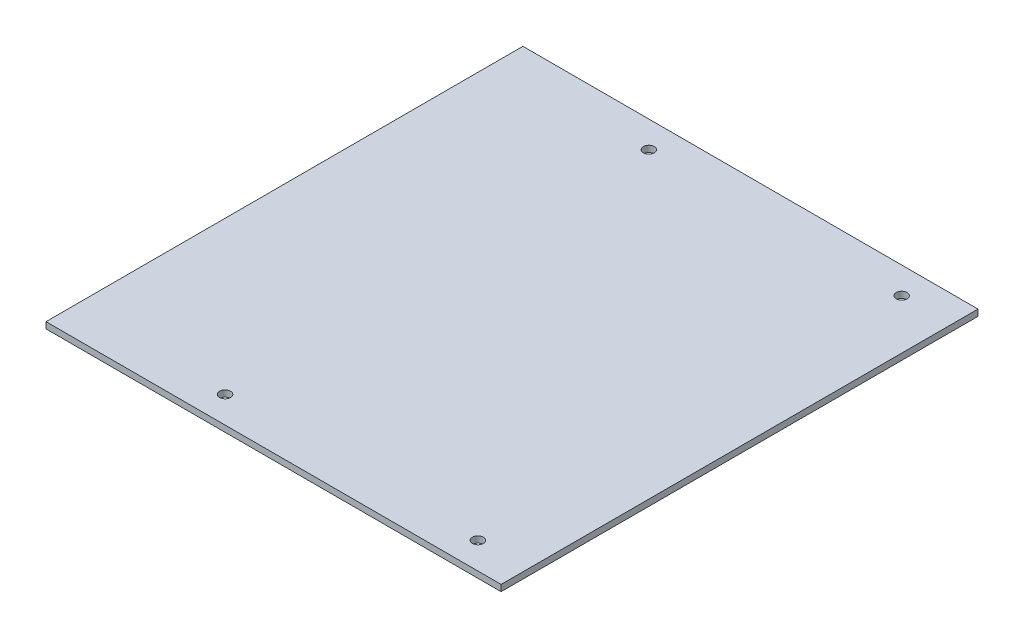
SolidWorks part; units mm, degrees
ref_plane "Front Plane" through (0, 0, 0) normal (0, 0, 1) x (1, 0, 0)
ref_plane "Top Plane" through (0, 0, 0) normal (0, 1, 0) x (1, 0, 0)
ref_plane "Right Plane" through (0, 0, 0) normal (1, 0, 0) x (0, 0, -1)
sketch "Sketch1" plane through (0, 0, 0) normal (0, 1, 0) x (1, 0, 0)
  line L1 (-140.35, -119.775) -> (-368.95, -119.775)
  line L2 (-140.35, -119.775) -> (-140.35, 119.775)
  line L3 (-140.35, 119.775) -> (-368.95, 119.775)
  line L4 (-368.95, -119.775) -> (-368.95, 119.775)
  line L5 (0, -3.8154) -> (0, 119.775) construction
  line L6 (361.3726, 119.775) -> (-361.3726, 119.775) construction
  line L7 (361.3726, -119.775) -> (-361.3726, -119.775) construction
  point P0 (0, 0)
  point P7 (-140.35, 0)
  point P9 (0, 0)
  dimension "D2" = 737.9
  dimension "D3" = 228.6
  dimension "D1" = 239.55
extrude "Boss-Extrude1" add sketch "Sketch1" along normal mid plane 3.175
hole_wizard "M5 Clearance Hole1" positions "Sketch4" profile "Sketch3" hole size "M5" standard "ANSI Metric" end condition through all
sketch "Sketch4" plane through (0, 1.5875, 0) normal (0, 1, 0) x (1, 0, 0)
  line L0 (-165.35, 106.425) -> (-165.35, -106.425) construction
  line L1 (-165.35, -106.425) -> (-292.35, -106.425) construction
  line L3 (-140.35, -119.775) -> (-140.35, 119.775) construction
  point P0 (-292.35, 106.425)
  point P2 (-165.35, 106.425)
  point P4 (-165.35, -106.425)
  point P6 (-292.35, -106.425)
  point P15 (-165.35, 0)
  dimension "D1" = 212.85
  dimension "D2" = 25
  dimension "D3" = 127
sketch "Sketch3" plane through (-292.35, 1.5875, -106.425) normal (1, 0, 0) x (0, 0, 1)
  line L0 (0, 0) -> (0, 3.175)
  line L1 (0, 3.175) -> (2.75, 3.175)
  line L2 (2.75, 3.175) -> (2.75, 0)
  line L5 (2.75, 0) -> (0, 0)
  line L11 (0, -6.35) -> (0, 107.95) construction
  dimension "Thru Hole Dia." = 5.5
  dimension "Thru Hole Depth" = 3.175
equation "\"Length\"= 28.5in"
equation "\"D2@Sketch1\"=\"Length\"+7*2mm"
